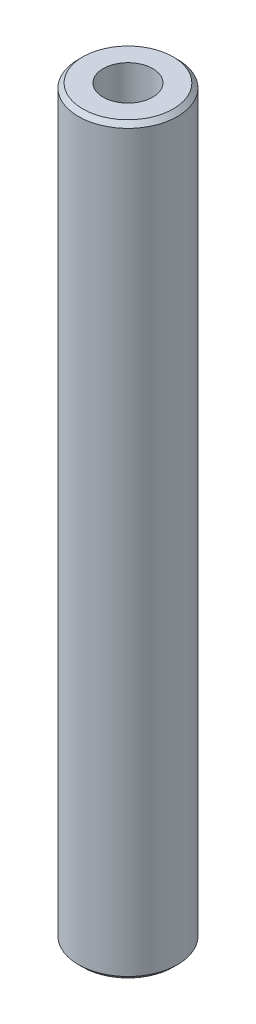
SolidWorks part; units mm, degrees
ref_plane "Front Plane" through (0, 0, 0) normal (0, 0, 1) x (1, 0, 0)
ref_plane "Top Plane" through (0, 0, 0) normal (0, 1, 0) x (1, 0, 0)
ref_plane "Right Plane" through (0, 0, 0) normal (1, 0, 0) x (0, 0, -1)
sketch "Sketch1" plane through (0, 0, 0) normal (0, 1, 0) x (1, 0, 0)
  circle A0 centre (0, 0) radius 40
  dimension "SHAFT_OD" = 80
extrude "Boss-Extrude1" add sketch "Sketch1" along normal blind 600
sketch "Sketch2" plane through (0, 0, 0) normal (0, 1, 0) x (1, 0, 0)
  circle A0 centre (0, 0) radius 20.0099
  dimension "BORE_D" = 40.0199
extrude "Cut-Extrude1" cut sketch "Sketch2" along normal through all
chamfer "Chamfer1" distance 3.5279 angle 45 2 edges at (0, 600, 40) (0, 0, 40)
